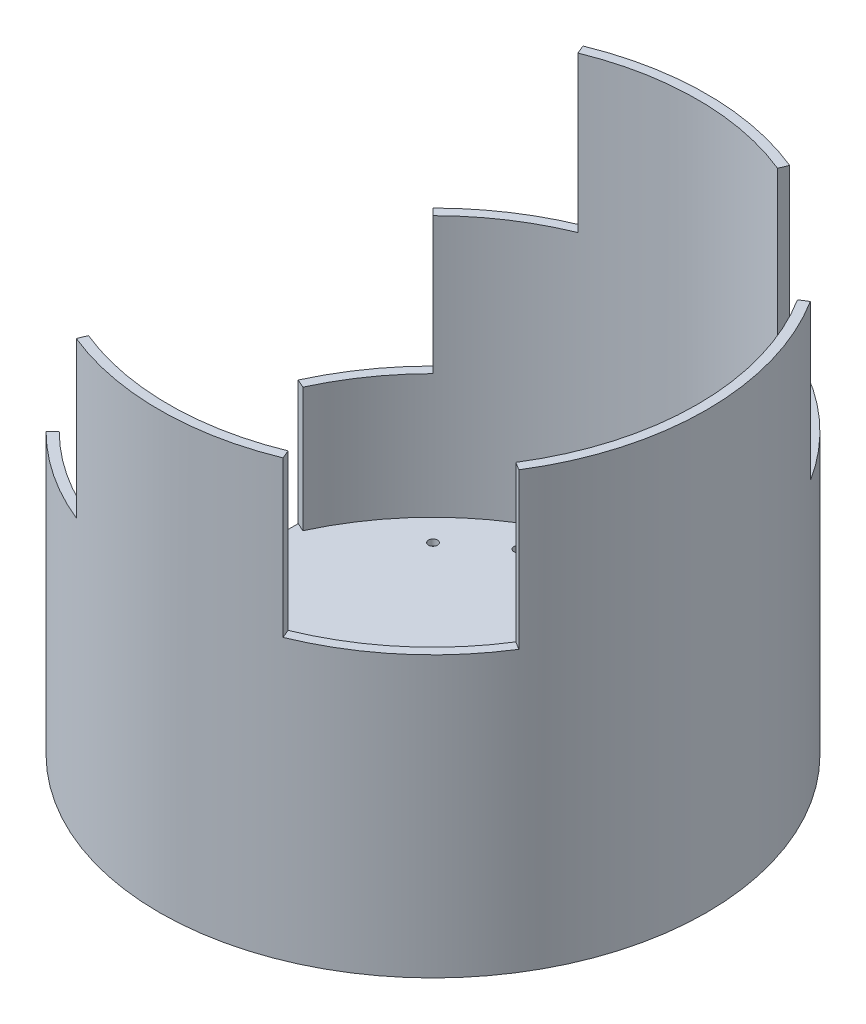
SolidWorks part; units mm, degrees
ref_plane "Plano frontal" through (0, 0, 0) normal (0, 0, 1) x (1, 0, 0)
ref_plane "Plano superior" through (0, 0, 0) normal (0, 1, 0) x (1, 0, 0)
ref_plane "Plano direito" through (0, 0, 0) normal (1, 0, 0) x (0, 0, -1)
sketch "Esboço1" plane through (0, 0, 0) normal (0, 1, 0) x (1, 0, 0)
  circle A0 centre (0, 0) radius 88
  dimension "D1" = 176
extrude "Ressalto-extrusão1" add sketch "Esboço1" along normal blind 6
sketch "Esboço3" plane through (0, 6, 0) normal (0, 1, 0) x (1, 0, 0)
  circle A0 centre (0, 0) radius 88
  circle A1 centre (0, 0) radius 85
  circle A2 centre (0, 0) radius 88 construction
  dimension "D2" = 170
extrude "Ressalto-extrusão2" add sketch "Esboço3" along normal blind 134
sketch "Esboço4" plane through (0, 140, 0) normal (0, 1, 0) x (1, 0, 0)
  line L0 (0, 0) -> (88, 0) construction
  line L1 (0, 0) -> (56.5653, 67.4119) construction
  line L2 (0, 0) -> (56.5653, -67.4119) construction
  line L3 (32.101, 78.7053) -> (71.9353, 45.2804)
  line L4 (34.9071, 85.5853) -> (78.2235, 49.2385)
  line L5 (78.2235, 49.2385) -> (71.9353, 45.2804)
  line L6 (34.9071, 85.5853) -> (32.101, 78.7053)
  line L7 (34.9071, -85.5853) -> (32.101, -78.7053)
  line L8 (78.2235, -49.2385) -> (71.9353, -45.2804)
  line L9 (34.9071, -85.5853) -> (78.2235, -49.2385)
  line L10 (32.101, -78.7053) -> (71.9353, -45.2804)
  line L11 (0, 0) -> (0, 88) construction
  line L12 (-32.101, -78.7053) -> (-71.9353, -45.2804)
  line L13 (-34.9071, -85.5853) -> (-78.2235, -49.2385)
  line L14 (-78.2235, -49.2385) -> (-71.9353, -45.2804)
  line L15 (-34.9071, -85.5853) -> (-32.101, -78.7053)
  line L16 (-34.9071, 85.5853) -> (-32.101, 78.7053)
  line L17 (-78.2235, 49.2385) -> (-71.9353, 45.2804)
  line L18 (-34.9071, 85.5853) -> (-78.2235, 49.2385)
  line L19 (-32.101, 78.7053) -> (-71.9353, 45.2804)
  circle A0 centre (0, 0) radius 88 construction
  circle A1 centre (0, 0) radius 85 construction
  point P13 (52.0182, 61.9928)
  point P16 (56.5653, 67.4119)
  point P20 (56.5653, -67.4119)
  point P21 (52.0182, -61.9928)
  point P27 (-52.0182, -61.9928)
  point P28 (-56.5653, -67.4119)
  point P33 (-56.5653, 67.4119)
  point P34 (-52.0182, 61.9928)
  dimension "D1" = 50
  dimension "D2" = 50
  dimension "D3" = 52
extrude "Corte-extrusão1" cut sketch "Esboço4" against normal blind 50
sketch "Esboço5" plane through (0, 140, 0) normal (0, 1, 0) x (1, 0, 0)
  line L0 (0, 0) -> (-80, 0) construction
  line L1 (-80, 36.6606) -> (-80, -36.6606) construction
  line L2 (-88, -36.6606) -> (-88, 36.6606)
  line L3 (-88, 36.6606) -> (-80, 36.6606)
  line L4 (-88, -36.6606) -> (-80, -36.6606)
  line L5 (-80, 36.6606) -> (-77.2727, 35.4108)
  line L6 (-80, -36.6606) -> (-77.2727, -35.4108)
  line L7 (-77.2727, -35.4108) -> (-77.2727, 35.4108)
  arc A0 (-74.4742, 46.8785) -> (-74.4742, -46.8785) centre (0, 0) ccw construction
  arc A1 (-71.9353, 45.2804) -> (-71.9353, -45.2804) centre (0, 0) ccw construction
  circle A2 centre (0, 0) radius 85 construction
  point P3 (-88, 0)
  point P9 (-80, 0)
  point P12 (-88, 0)
  dimension "D1" = 80
extrude "Corte-extrusão2" cut sketch "Esboço5" against normal through all
sketch "Esboço6" plane through (0, 0, 0) normal (0, 1, 0) x (1, 0, 0)
  line L0 (-80, 36.6606) -> (-77.2727, 35.4108)
  line L1 (-77.2727, 35.4108) -> (-77.2727, -35.4108)
  line L2 (-77.2727, -35.4108) -> (-77.2727, 35.4108) construction
  line L3 (-77.2727, -35.4108) -> (-80, -36.6606)
  line L4 (-80, -36.6606) -> (-80, 36.6606)
extrude "Ressalto-extrusão3" add sketch "Esboço6" along normal offset from surface (46 mm away) 40 up to face at (3.8636, 6, 0) offset beyond the face yes
sketch "Esboço7" plane through (0, 140, 0) normal (0, 1, 0) x (1, 0, 0)
  line L0 (-74.4742, 46.8785) -> (-71.9353, 45.2804)
  line L1 (-71.9353, 45.2804) -> (-71.9353, -45.2804)
  line L2 (-71.9353, -45.2804) -> (-74.4742, -46.8785)
  line L3 (-74.4742, -46.8785) -> (-80, -46.8785)
  line L4 (-80, -46.8785) -> (-80, 46.8785)
  line L5 (-80, 46.8785) -> (-74.4742, 46.8785)
extrude "Corte-extrusão3" cut sketch "Esboço7" against normal up to surface (94 mm away) up to face at (-78.6364, 46, 0)
sketch "Esboço8" plane through (0, 140, 0) normal (0, 1, 0) x (1, 0, 0)
  line L0 (0, 0) -> (-80, 0) construction
  line L1 (-80, 36.6606) -> (-80, -36.6606) construction
  line L2 (0, 0) -> (-60.1041, 60.1041) construction
  line L3 (-60.1041, 60.1041) -> (-62.2254, 62.2254)
  line L4 (-62.2254, 62.2254) -> (-80, 62.2254)
  line L5 (-60.1041, 60.1041) -> (-60.1041, -60.1041)
  line L6 (-60.1041, -60.1041) -> (-62.2254, -62.2254)
  line L7 (-62.2254, -62.2254) -> (-80, -62.2254)
  line L8 (-80, -62.2254) -> (-80, 62.2254)
  arc A0 (-32.101, 78.7053) -> (-71.9353, 45.2804) centre (0, 0) ccw construction
  arc A6 (-77.2727, -35.4108) -> (-77.2727, 35.4108) centre (0, 0) ccw construction
  arc A7 (-33.234, 81.4831) -> (-74.4742, 46.8785) centre (0, 0) ccw construction
  point P12 (-62.2254, -62.6342)
  dimension "D1" = 45
  dimension "D2" = 3
  dimension "D3" = 45
extrude "Corte-extrusão4" cut sketch "Esboço8" against normal up to surface (94 mm away) up to face at (-76.0035, 46, 0)
sketch "Esboço9" plane through (0, 46, 0) normal (0, 1, 0) x (1, 0, 0)
  line L0 (-77.2727, 35.4108) -> (-80, 36.6606)
  line L1 (-80, 36.6606) -> (-80, -36.6606)
  line L2 (-80, -36.6606) -> (-77.2727, -35.4108)
  line L3 (-77.2727, -35.4108) -> (-77.2727, 35.4108)
extrude "Corte-extrusão5" cut sketch "Esboço9" against normal up to surface (40 mm away) up to face at (3.8636, 6, 0)
sketch "Esboço10" plane through (0, 0, 0) normal (0, -1, 0) x (1, 0, 0)
  line L0 (0, 0) -> (-55, 0) construction
  line L1 (-55, -64.8074) -> (-55, 64.8074)
  arc A0 (-55, -64.8074) -> (-55, 64.8074) centre (0, 0) ccw
  point P7 (-55, 0)
  dimension "D1" = 170
  dimension "D2" = 55
extrude "Corte-extrusão6" cut sketch "Esboço10" against normal blind 4
sketch "Esboço11" plane through (0, 6, 0) normal (0, 1, 0) x (1, 0, 0)
  line L0 (0, 0) -> (-80, 0) construction
  line L1 (-80, -36.6606) -> (-80, 36.6606) construction
  line L2 (0, 0) -> (-53.033, 53.033) construction
  line L3 (0, 0) -> (-37.5, 64.9519) construction
  line L4 (0, 0) -> (37.5, 64.9519) construction
  line L5 (0, 0) -> (57.4533, 48.2091) construction
  line L6 (0, 0) -> (0, 88) construction
  line L7 (0, 0) -> (57.4533, -48.2091) construction
  line L8 (0, 0) -> (37.5, -64.9519) construction
  line L9 (0, 0) -> (-37.5, -64.9519) construction
  line L10 (0, 0) -> (-53.033, -53.033) construction
  arc A0 (33.234, 81.4831) -> (-33.234, 81.4831) centre (0, 0) ccw construction
  dimension "D1" = 45
  dimension "D2" = 30
  dimension "D3" = 30
  dimension "D4" = 50
  dimension "D5" = 75
hole_wizard "Furo com folga de M2.51" positions "3DSketch1" profile "Esboço12" hole size "M2.5" standard "ISO"
sketch3d "3DSketch1"
  point P0 (-53.033, 6, -53.033)
  point P3 (-37.5, 6, -64.9519)
  point P6 (37.5, 6, -64.9519)
  point P9 (57.4533, 6, -48.2091)
  point P13 (-53.033, 6, 53.033)
  point P16 (-37.5, 6, 64.9519)
  point P19 (37.5, 6, 64.9519)
  point P22 (57.4533, 6, 48.2091)
sketch "Esboço12" plane through (-53.033, 6, -53.033) normal (1, 0, 0) x (0, 0, 1)
  line L0 (0, 0) -> (0, 4.8712)
  line L1 (0, 4.8712) -> (1.45, 4)
  line L2 (1.45, 4) -> (1.45, 0)
  line L5 (1.45, 0) -> (0, 0)
  line L10 (0, 4.8712) -> (-1.45, 4) construction
  line L11 (0, -6.35) -> (0, 107.95) construction
  dimension "Hole Dia." = 2.9
  dimension "Hole Depth" = 4
  dimension "Drill Angle" = 118
